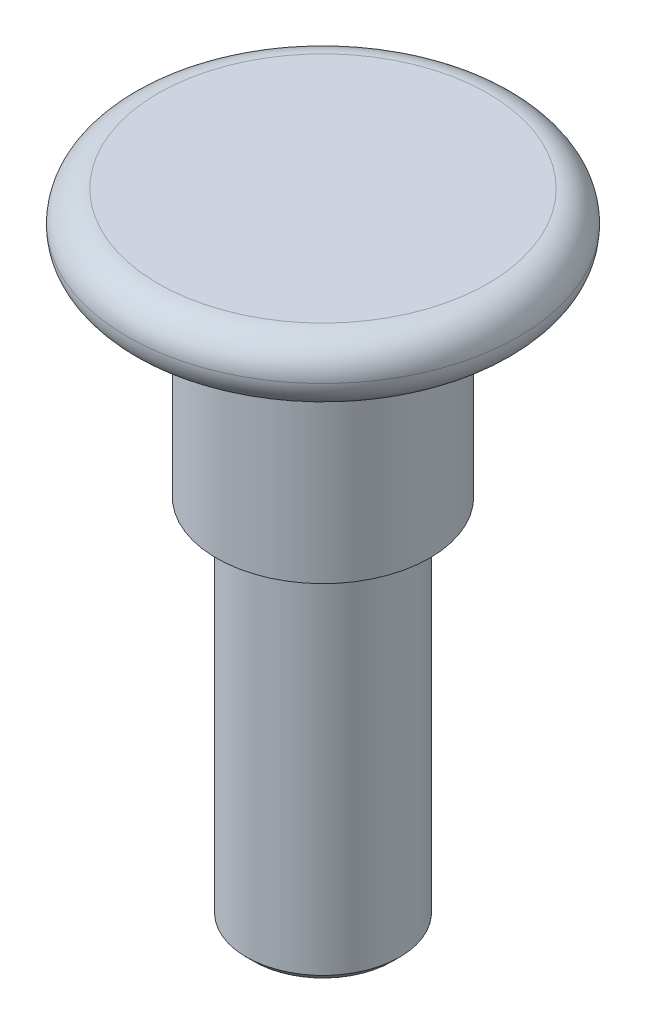
SolidWorks part; units mm, degrees
ref_plane "Plano frontal" through (0, 0, 0) normal (0, 0, 1) x (1, 0, 0)
ref_plane "Plano superior" through (0, 0, 0) normal (0, 1, 0) x (1, 0, 0)
ref_plane "Plano direito" through (0, 0, 0) normal (1, 0, 0) x (0, 0, -1)
sketch "Esboço1" plane through (0, 0, 0) normal (0, 0, 1) x (1, 0, 0)
  line L0 (0, -52.7198) -> (0, 61.8362) construction
  line L1 (0, 61.8362) -> (12.75, 61.8362)
  line L2 (12.75, 61.8362) -> (12.75, 57.8362)
  line L3 (6.95, 44.4362) -> (6.95, 57.8362)
  line L4 (6.95, 57.8362) -> (12.75, 57.8362)
  line L5 (6.95, 44.4362) -> (5, 44.4362)
  line L6 (5, 44.4362) -> (5, 20.4362)
  line L7 (5, 20.4362) -> (2, 20.4362)
  line L8 (2, 20.4362) -> (2, 29.4362)
  line L9 (2, 29.4362) -> (0, 30.6862)
  line L10 (0, 61.8362) -> (0, 30.6862)
  dimension "D1" = 4
  dimension "D2" = 13.4
  dimension "D3" = 24
  dimension "D4" = 9
  dimension "D5" = 10.25
  dimension "D6" = 2
  dimension "D7" = 5
  dimension "D9" = 12.75
revolve "Revolução1" add sketch "Esboço1" angle 360 about L0
fillet "Filete1" radius 2 2 edges at (12.75, 57.8362, 0) (12.75, 61.8362, 0)
chamfer "Chanfro1" distance 0.5 angle 45 1 edges at (5, 20.4362, 0)
